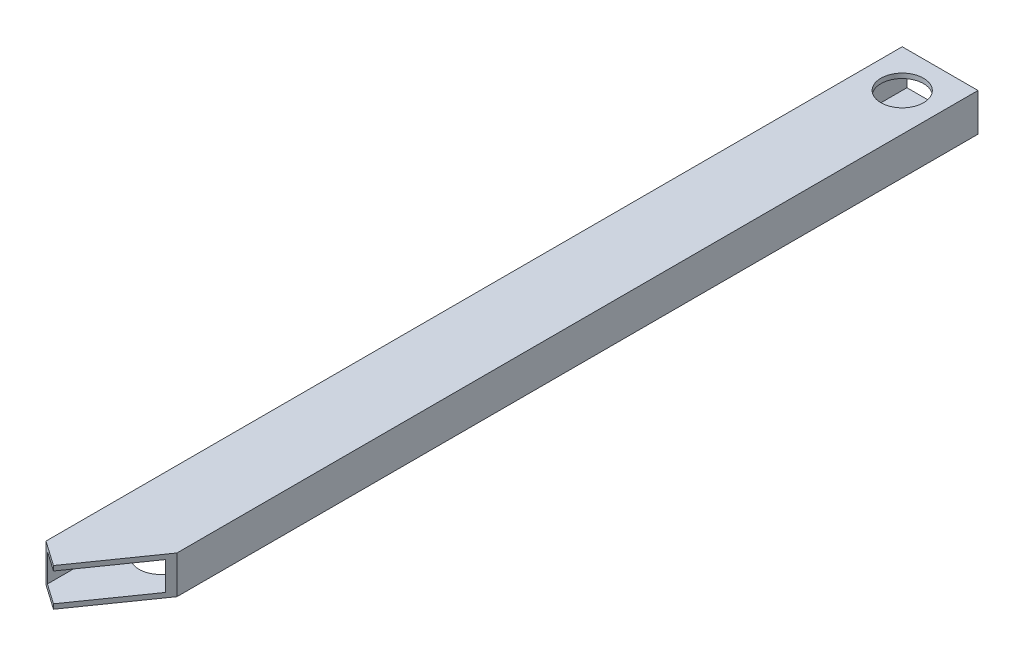
SolidWorks part; units mm, degrees
ref_plane "Front Plane" through (0, 0, 0) normal (0, 0, 1) x (1, 0, 0)
ref_plane "Top Plane" through (0, 0, 0) normal (0, 1, 0) x (1, 0, 0)
ref_plane "Right Plane" through (0, 0, 0) normal (1, 0, 0) x (0, 0, -1)
sketch "Sketch1" plane through (0, 0, 0) normal (0, 0, 1) x (1, 0, 0)
  line L1 (0, 0) -> (50.8, 0)
  line L2 (0, 0) -> (0, 25.4)
  line L3 (0, 25.4) -> (50.8, 25.4)
  line L4 (50.8, 0) -> (50.8, 25.4)
extrude "Boss-Extrude1" add sketch "Sketch1" along normal blind 609.6
sketch "Sketch2" plane through (0, 0, 0) normal (0, 0, -1) x (-1, 0, 0)
  line L1 (-3.175, 3.175) -> (-47.625, 3.175)
  line L2 (-3.175, 3.175) -> (-3.175, 22.225)
  line L3 (-3.175, 22.225) -> (-47.625, 22.225)
  line L4 (-47.625, 3.175) -> (-47.625, 22.225)
extrude "Cut-Extrude1" cut sketch "Sketch2" against normal blind 609.6
sketch "Sketch6" plane through (0, 25.4, 0) normal (0, 1, 0) x (1, 0, 0)
  line L0 (25.4, 0) -> (25.4, -25.4) construction
  line L1 (50.8, 0) -> (0, 0) construction
  circle A0 centre (25.4, -25.4) radius 14.2875
extrude "Cut-Extrude5" cut sketch "Sketch6" against normal blind 25.4
sketch "Sketch7" plane through (0, 25.4, 0) normal (0, 1, 0) x (1, 0, 0)
  line L1 (50.8, -609.6) -> (50.8, 0) construction
  line L2 (50.8, -537.0501) -> (50.8, -609.6)
  line L3 (50.8, -609.6) -> (0, -609.6)
  line L5 (0, -609.6) -> (0, 0) construction
  line L6 (0, -574.0295) -> (16.7127, -585.7318)
  line L7 (16.7127, -585.7318) -> (50.8, -537.0501)
  line L8 (0, -574.0295) -> (0, -609.6)
extrude "Cut-Extrude6" cut sketch "Sketch7" against normal blind 25.4
sketch "Sketch8" plane through (0, 0, 0) normal (0, -1, 0) x (1, 0, 0)
  line L0 (50.8, 537.0501) -> (0, 537.0501) construction
  line L1 (0, 574.0295) -> (0, 0) construction
  line L2 (25.4, 537.0501) -> (25.4, 508.4751) construction
  circle A0 centre (25.4, 522.7626) radius 14.2875
extrude "Cut-Extrude7" cut sketch "Sketch8" against normal blind 3.175
